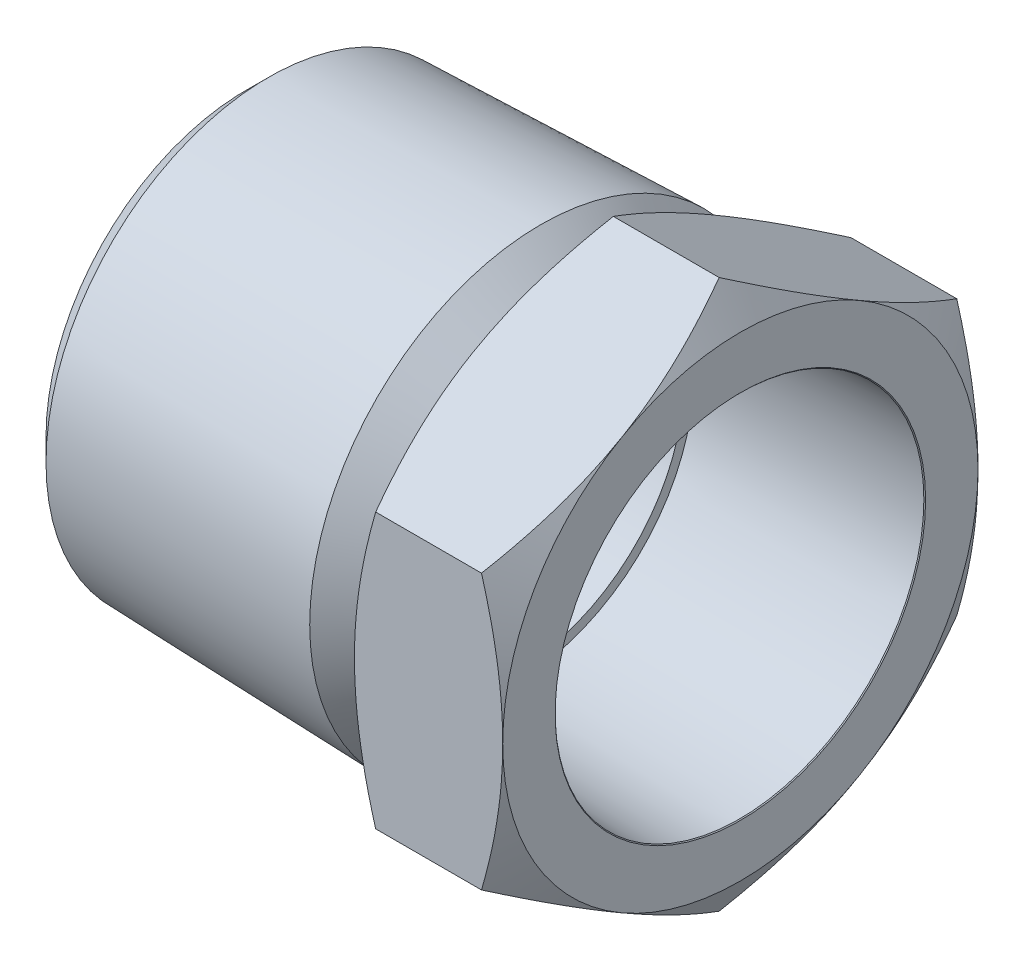
SolidWorks part; units mm, degrees
ref_plane "Front" through (0, 0, 0) normal (0, 0, 1) x (1, 0, 0)
ref_plane "Top" through (0, 0, 0) normal (0, 1, 0) x (1, 0, 0)
ref_plane "Right" through (0, 0, 0) normal (1, 0, 0) x (0, 0, -1)
sketch "Sketch1" plane through (0, 0, 0) normal (0, 0, 1) x (1, 0, 0)
  line L0 (-14.859, 0) -> (14.859, 0) construction
ref_plane "Plane1" through (-14.859, 0, 0) normal (1, 0, 0) x (0, 0, -1)
sketch "Sketch2" plane through (-14.859, 0, 0) normal (1, 0, 0) x (0, 0, -1)
  circle A0 centre (0, 0) radius 13.335
  dimension "OD" = 26.67
extrude "Extrude1" add sketch "Sketch2" along normal up to vertex (29.718 mm away) draft 1.783 up to point (14.859, 0, 0) draft outward yes
sketch "Sketch3" plane through (-14.859, 0, 0) normal (-1, 0, 0) x (0, 0, 1)
  circle A1 centre (0, 0) radius 13.335
  circle A2 centre (0, 0) radius 13.335
  dimension "D1" = 0
curve "Helix/Spiral1" parameters "pitch"=1.8143
sketch "Sketch4" plane through (0, 0, 0) normal (0, 0, 1) x (1, 0, 0)
  line L0 (-16.4465, 13.335) -> (-15.7661, 12.1566)
  line L1 (-15.7661, 12.1566) -> (-15.5394, 12.1566)
  line L2 (-15.5394, 12.1566) -> (-14.859, 13.335)
  line L3 (-16.4465, 13.335) -> (-14.859, 13.335) construction
  line L4 (-16.1063, 12.7458) -> (-15.1992, 12.7458) construction
  line L5 (-15.6527, 12.1566) -> (-15.6527, 13.335) construction
  line L6 (-16.4465, 13.335) -> (-14.6791, 13.6466)
  line L7 (-14.859, 13.335) -> (-14.6791, 13.6466)
  line L8 (-14.859, 13.335) -> (-14.859, -13.335) construction
  dimension "D1" = 10
  dimension "D2" = 0.2268
  dimension "D3" = 0.9071
  dimension "D4" = 60
sweep "Cut-Sweep1" [suppressed] cut profiles "Sketch4" path "Helix/Spiral1"
sketch "Sketch5" plane through (-14.859, 0, 0) normal (1, 0, 0) x (0, 0, -1)
  circle A0 centre (0, 0) radius 12.1566 construction
  circle A1 centre (0, 0) radius 12.0296
  dimension "D1" = 0.127
extrude "Cut-Extrude1" cut sketch "Sketch5" along normal through all draft 45 flip side to cut
ref_plane "Plane2" through (14.859, 0, 0) normal (1, 0, 0) x (0, 0, -1)
ref_plane "Plane3" through (5.9436, 0, 0) normal (1, 0, 0) x (0, 0, -1)
sketch "Sketch8" plane through (5.9436, 0, 0) normal (1, 0, 0) x (0, 0, -1)
  circle A2 centre (0, 0) radius 19.685
  circle A3 centre (0, 0) radius 19.685
  dimension "D1" = 6.35
extrude "Cut-Extrude4" cut sketch "Sketch8" along normal through all
sketch "Sketch9" plane through (5.9436, 0, 0) normal (1, 0, 0) x (0, 0, -1)
  circle A0 centre (0, 0) radius 13.335 construction
  circle A2 centre (0, 0) radius 12.1566
extrude "Cut-Extrude5" cut sketch "Sketch9" against normal blind 1.3607 flip side to cut
ref_plane "Plane4" through (4.5829, 0, 0) normal (1, 0, 0) x (0, 0, -1)
sketch "Sketch10" plane through (4.5829, 0, 0) normal (1, 0, 0) x (0, 0, -1)
  circle A1 centre (0, 0) radius 12.1566
  circle A2 centre (0, 0) radius 12.1566
  dimension "D1" = 0
extrude "Cut-Extrude6" cut sketch "Sketch10" against normal through all draft 45 flip side to cut
sketch "Sketch6" plane through (14.859, 0, 0) normal (1, 0, 0) x (0, 0, -1)
  line L1 (0, 16.4978) -> (-14.2875, 8.2489)
  line L2 (-14.2875, 8.2489) -> (-14.2875, -8.2489)
  line L3 (-14.2875, -8.2489) -> (0, -16.4978)
  line L4 (0, -16.4978) -> (14.2875, -8.2489)
  line L5 (14.2875, -8.2489) -> (14.2875, 8.2489)
  line L6 (14.2875, 8.2489) -> (0, 16.4978)
  circle A0 centre (0, 0) radius 14.2875 construction
  dimension "Hex" = 28.575
extrude "Extrude2" add sketch "Sketch6" against normal blind 8.9154
sketch "Sketch7" plane through (14.859, 0, 0) normal (1, 0, 0) x (0, 0, -1)
  line L0 (0, 16.4978) -> (-14.2875, 8.2489) construction
  circle A0 centre (0, 0) radius 14.2875
extrude "Cut-Extrude2" cut sketch "Sketch7" against normal through all draft 60 flip side to cut
sketch "Sketch18" plane through (5.9436, 0, 0) normal (-1, 0, 0) x (0, 0, 1)
  circle A0 centre (0, 0) radius 14.2875 construction
  circle A1 centre (0, 0) radius 14.2875
extrude "Extrude3" cut sketch "Sketch18" against normal blind 10 draft 60 flip side to cut
ref_plane "Plane5" through (1.397, 0, 0) normal (1, 0, 0) x (0, 0, -1)
sketch "Sketch11" plane through (1.397, 0, 0) normal (1, 0, 0) x (0, 0, -1)
  circle A0 centre (0, 0) radius 10.668
  dimension "OD2" = 21.336
extrude "Cut-Extrude7" cut sketch "Sketch11" along normal through all draft 1.783 draft outward yes
sketch "Sketch12" plane through (1.397, 0, 0) normal (1, 0, 0) x (0, 0, -1)
  circle A0 centre (0, 0) radius 10.668 construction
  circle A1 centre (0, 0) radius 10.668
curve "Helix/Spiral2" parameters "pitch 2"=1.8143
sketch "Sketch16" plane through (14.859, 0, 0) normal (1, 0, 0) x (0, 0, -1)
  circle A2 centre (0, 0) radius 11.1379
  circle A3 centre (0, 0) radius 11.1379
  dimension "D1" = 0.0508
sketch "Sketch14" plane through (0, 0, 0) normal (0, 0, 1) x (1, 0, 0)
  line L0 (-0.1905, 10.668) -> (1.397, 10.668) construction
  line L1 (1.397, 10.668) -> (0.7166, 9.4896) construction
  line L2 (0.7166, 9.4896) -> (0.4899, 9.4896)
  line L3 (0.4899, 9.4896) -> (-0.1905, 10.668)
  line L4 (0.1497, 10.0788) -> (1.0568, 10.0788) construction
  line L5 (0.6033, 9.4896) -> (0.6033, 10.668) construction
  line L6 (-0.1905, 10.668) -> (1.5769, 10.9796)
  line L7 (1.5769, 10.9796) -> (0.7166, 9.4896)
  line L8 (1.397, -10.668) -> (1.397, 10.668) construction
  dimension "D1" = 10
  dimension "D2" = 60
  dimension "D3" = 0.2268
  dimension "D4" = 0.9071
sweep "Sweep1" [suppressed] add profiles "Sketch14" path "Helix/Spiral2"
sketch "Sketch15" plane through (14.859, 0, 0) normal (1, 0, 0) x (0, 0, -1)
  line L6 (0, 16.4978) -> (-14.2875, 8.2489)
  line L7 (-14.2875, 8.2489) -> (-14.2875, -8.2489)
  line L8 (-14.2875, -8.2489) -> (0, -16.4978)
  line L9 (0, -16.4978) -> (14.2875, -8.2489)
  line L10 (14.2875, -8.2489) -> (14.2875, 8.2489)
  line L11 (14.2875, 8.2489) -> (0, 16.4978)
  line L12 (0, 16.4978) -> (-14.2875, 8.2489)
  line L13 (-14.2875, 8.2489) -> (-14.2875, -8.2489)
  line L14 (-14.2875, -8.2489) -> (0, -16.4978)
  line L15 (0, -16.4978) -> (14.2875, -8.2489)
  line L16 (14.2875, -8.2489) -> (14.2875, 8.2489)
  line L17 (14.2875, 8.2489) -> (0, 16.4978)
  dimension "D1" = 0
extrude "Cut-Extrude8" [suppressed] cut sketch "Sketch15" along normal through all
extrude "Cut-Extrude9" cut sketch "Sketch16" against normal blind 6.35 draft 45
sketch "Sketch17" plane through (0, 0, 0) normal (0, 0, 1) x (1, 0, 0)
  line L1 (-14.859, 10.0788) -> (1.397, 10.0788)
  line L2 (1.397, 10.0788) -> (1.397, 0)
  line L3 (1.397, 0) -> (-14.859, 0)
  line L4 (-14.859, 0) -> (-14.859, 10.0788)
  line L5 (-14.859, -13.335) -> (-14.859, 13.335) construction
  line L6 (1.397, -10.668) -> (1.397, 10.668) construction
revolve "Cut-Revolve1" cut sketch "Sketch17" angle 360 about L0
equation "\"D3@Helix/Spiral1\" = \"L@Sketch1\""
equation "\"D2@Sketch4\" = \"pitch@Helix/Spiral1\"*.125"
equation "\"D3@Sketch4\" = \"pitch@Helix/Spiral1\"*.5"
equation "\"D1@Extrude2\" = \"L@Sketch1\"*.3"
equation "\"D1@Plane3\" = \"D1@Extrude2\""
equation "\"D1@Cut-Extrude5\" = \"pitch@Helix/Spiral1\"*.75"
equation "\"D1@Plane4\" = \"D1@Cut-Extrude5\""
equation "\"D3@Helix/Spiral2\" = \"thread engagement @Plane5\"+.250"
equation "\"D3@Sketch14\" = \"pitch 2@Helix/Spiral2\"*.125"
equation "\"D4@Sketch14\" = \"pitch 2@Helix/Spiral2\"*.50"
